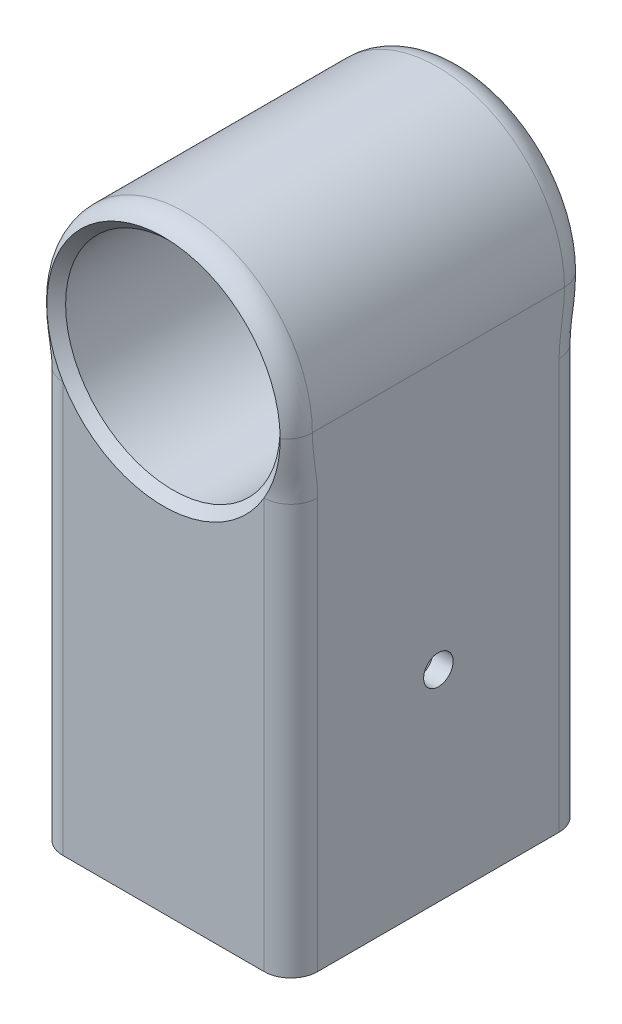
SolidWorks part; units mm, degrees
material "ABS"
ref_plane "Front Plane" through (0, 0, 0) normal (0, 0, 1) x (1, 0, 0)
ref_plane "Top Plane" through (0, 0, 0) normal (0, 1, 0) x (1, 0, 0)
ref_plane "Right Plane" through (0, 0, 0) normal (1, 0, 0) x (0, 0, -1)
sketch "Sketch1" plane through (0, 0, 0) normal (0, 0, 1) x (1, 0, 0)
  line L0 (-9.5, 0) -> (-9.5, -35)
  line L3 (-9.5, -35) -> (9.5, -35)
  line L4 (9.5, -35) -> (9.5, 0)
  circle A0 centre (0, 0) radius 8
  circle A1 centre (0, 0) radius 9.5
  dimension "D1" = 16
  dimension "D2" = 19
  dimension "D3" = 35
extrude "Boss-Extrude1" add sketch "Sketch1" along normal blind 22 contours A1 | A1 A0 region at (0, -21.149, 0) region at (0, 9.2313, 0)
sketch "Sketch3" plane through (0, -35, 0) normal (0, -1, 0) x (1, 0, 0)
  line L0 (-9.5, 0) -> (9.5, 0) construction
  circle A0 centre (0, 11) radius 8.1
  dimension "D2" = 16.2
  dimension "D1" = 11
extrude "Cut-Extrude1" cut sketch "Sketch3" against normal blind 20
chamfer "Chamfer1" distance 0.7 angle 45 3 edges at (8, 0, 0) (8, 0, 22) (0, -35, 2.9)
sketch "Sketch4" plane through (-9.5, 0, 0) normal (-1, 0, 0) x (0, 0, 1)
  line L0 (0, 0) -> (0, -35) construction
  line L1 (22, -35) -> (0, -35) construction
  circle A0 centre (11, -20) radius 1.1
  dimension "D2" = 2.2
  dimension "D1" = 11
  dimension "D3" = 15
extrude "Cut-Extrude2" cut sketch "Sketch4" against normal blind 30
fillet "Fillet1" radius 2 4 edges at (-9.5, -17.5, 0) (-9.5, -17.5, 22) (9.5, -17.5, 0) (9.5, -17.5, 22)
